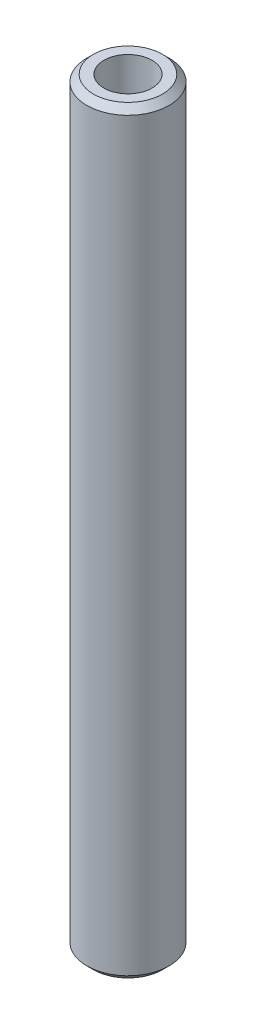
SolidWorks part; units mm, degrees
ref_plane "Front Plane" through (0, 0, 0) normal (0, 0, 1) x (1, 0, 0)
ref_plane "Top Plane" through (0, 0, 0) normal (0, 1, 0) x (1, 0, 0)
ref_plane "Right Plane" through (0, 0, 0) normal (1, 0, 0) x (0, 0, -1)
sketch "Sketch1" plane through (0, 0, 0) normal (0, 1, 0) x (1, 0, 0)
  circle A0 centre (0, 0) radius 15
  dimension "SHAFT_OD" = 30
extrude "Boss-Extrude1" add sketch "Sketch1" along normal blind 276.8169
sketch "Sketch2" plane through (0, 0, 0) normal (0, 1, 0) x (1, 0, 0)
  circle A0 centre (0, 0) radius 8.8003
  dimension "BORE_D" = 17.6007
extrude "Cut-Extrude1" cut sketch "Sketch2" along normal through all
chamfer "Chamfer1" distance 2.3976 angle 45 2 edges at (0, 276.8169, 15) (0, 0, 15)
